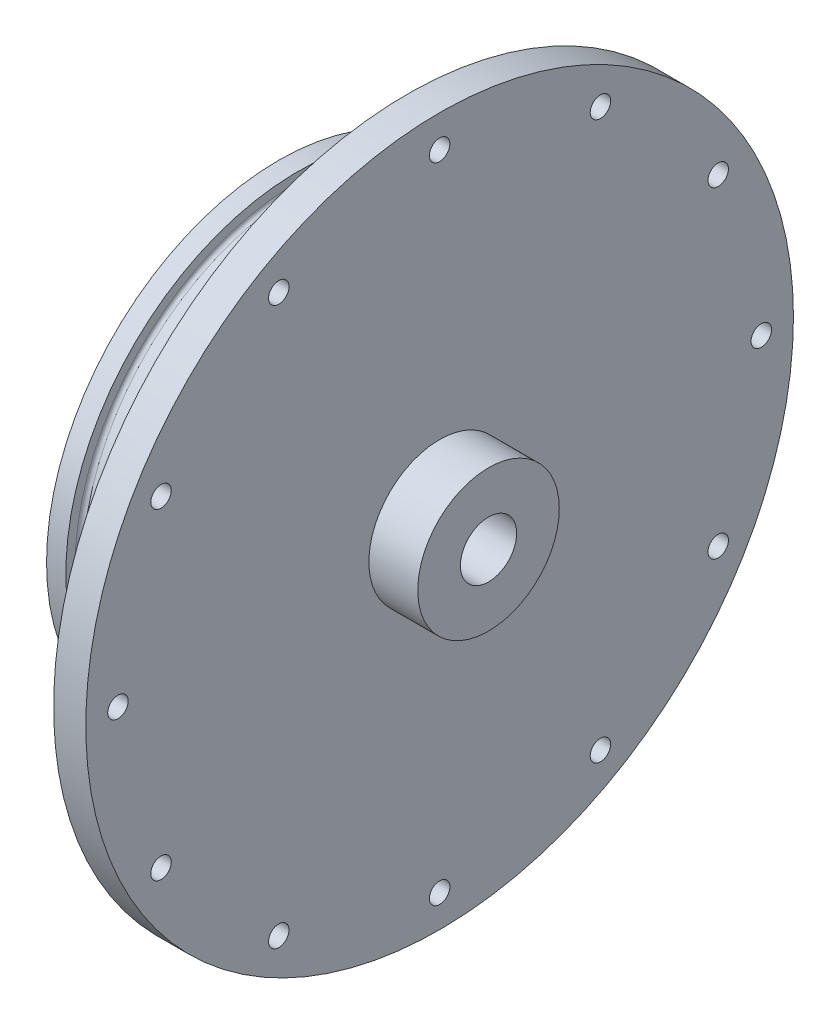
SolidWorks part; units mm, degrees
material "7075-T6 (SN)"
ref_plane "Front Plane" through (0, 0, 0) normal (0, 0, 1) x (1, 0, 0)
ref_plane "Top Plane" through (0, 0, 0) normal (0, 1, 0) x (1, 0, 0)
ref_plane "Right Plane" through (0, 0, 0) normal (1, 0, 0) x (0, 0, -1)
sketch "Sketch1" plane through (0, 0, 0) normal (1, 0, 0) x (0, 0, -1)
  circle A0 centre (0, 0) radius 69.85
  dimension "D1" = 139.7
extrude "Boss-Extrude1" add sketch "Sketch1" along normal blind 6.35
sketch "Sketch2" plane through (0, 0, 0) normal (-1, 0, 0) x (0, 0, 1)
  circle A0 centre (0, 0) radius 45.847
  dimension "D1" = 91.694
extrude "Boss-Extrude2" add sketch "Sketch2" along normal blind 25.4
sketch "Sketch10" plane through (0, 0, 0) normal (0, 1, 0) x (1, 0, 0)
  line L0 (0, 0) -> (-53.2238, 0) construction
  line L1 (-26.2636, 0) -> (26.2636, 0) construction
  line L2 (0, 0) -> (0, 64.5447) construction
  line L3 (0, -62.865) -> (0, 62.865) construction
ref_plane "Plane1" through (0, 0, -45.847) normal (0, 0, -1) x (-1, 0, 0)
sketch "Sketch11" plane through (0, 0, -45.847) normal (0, 0, -1) x (-1, 0, 0)
  line L0 (0, 0) -> (53.2238, 0) construction
  line L1 (0, -45.847) -> (0, 45.847) construction
  circle A0 centre (7.62, 0) radius 1.8986
  dimension "D2" = 3.7973
  dimension "D1" = 7.62
extrude "Cut-Extrude3" cut sketch "Sketch11" against normal blind 10.16
pattern_circular "CirPattern1" count 12 over 360 about axis through (0, 0, 0) along (-1, 0, 0) of "Cut-Extrude3" reverse direction yes
sketch "Sketch15" plane through (6.35, 0, 0) normal (1, 0, 0) x (0, 0, -1)
  circle A0 centre (0, 0) radius 5.5562
  dimension "D1" = 11.1125
extrude "Cut-Extrude4" cut sketch "Sketch15" against normal through all both and the other way through all
sketch "Sketch16" plane through (0, 0, 0) normal (0, 0, 1) x (1, 0, 0)
  line L0 (-9.5186, 45.847) -> (-25.4, 45.847) construction
  line L1 (-21.59, 45.847) -> (-14.4018, 45.847)
  line L2 (-21.59, 45.847) -> (-21.59, 44.069)
  line L3 (-20.828, 43.307) -> (-15.1638, 43.307)
  line L4 (-14.4018, 45.847) -> (-14.4018, 44.069)
  line L5 (0, 0) -> (-53.2238, 0) construction
  line L6 (-25.4, 45.847) -> (-25.4, -45.847) construction
  arc A0 (-14.4018, 44.069) -> (-15.1638, 43.307) centre (-15.1638, 44.069) cw
  arc A1 (-20.828, 43.307) -> (-21.59, 44.069) centre (-20.828, 44.069) cw
  point P8 (-26.6119, 0)
  point P13 (-14.4018, 43.307)
  point P16 (-21.59, 43.307)
  dimension "D4" = 0.762
  dimension "D1" = 43.307
  dimension "D2" = 3.81
  dimension "D3" = 7.1882
revolve "Cut-Revolve1" cut sketch "Sketch16" angle 360 about L0
sketch "Sketch17" plane through (6.35, 0, 0) normal (1, 0, 0) x (0, 0, -1)
  circle A0 centre (0, 0) radius 13.97
  circle A1 centre (0, 0) radius 5.5562
  dimension "D1" = 27.94
  dimension "D2" = 11.1125
extrude "Boss-Extrude3" add sketch "Sketch17" along normal blind 9.652
cosmetic thread "Cosmetic Thread1" parameters "D2"=23.1953
sketch "Sketch18" plane through (-25.4, 0, 0) normal (-1, 0, 0) x (0, 0, 1)
  circle A0 centre (0, 0) radius 38.2905
  dimension "D1" = 76.581
extrude "Cut-Extrude5" cut sketch "Sketch18" against normal blind 6.604
sketch "Sketch19" plane through (-18.796, 0, 0) normal (-1, 0, 0) x (0, 0, 1)
  line L0 (0, 0) -> (0, 69.85) construction
  circle A0 centre (0, 0) radius 69.85 construction
  circle A1 centre (0, 33.3375) radius 1.1303
  circle A2 centre (23.5732, 23.5732) radius 1.1303
  circle A3 centre (33.3375, 0) radius 1.1303
  circle A4 centre (23.5732, -23.5732) radius 1.1303
  circle A5 centre (0, -33.3375) radius 1.1303
  circle A6 centre (-23.5732, -23.5732) radius 1.1303
  circle A7 centre (-33.3375, 0) radius 1.1303
  circle A8 centre (-23.5732, 23.5732) radius 1.1303
  point P24 (0, 0)
  dimension "D2" = 2.2606
  dimension "D1" = 33.3375
  dimension "D3" = 8
extrude "Cut-Extrude6" cut sketch "Sketch19" against normal blind 6.35
sketch "Sketch20" plane through (-18.796, 0, 0) normal (-1, 0, 0) x (0, 0, 1)
  circle A0 centre (0, 0) radius 23.495
  dimension "D1" = 46.99
extrude "Cut-Extrude7" cut sketch "Sketch20" against normal blind 19.05
fillet "Fillet1" radius 2.54 1 edges at (0.254, 0, 23.495)
chamfer "Chamfer1" distance 5.08 angle 45 1 edges at (0.254, 0, 5.5562)
sketch "Sketch21" plane through (6.35, 0, 0) normal (1, 0, 0) x (0, 0, -1)
  line L0 (0, 0) -> (0, 75.052) construction
  circle A0 centre (0, 63.5) radius 2.0193
  circle A1 centre (31.75, 54.9926) radius 2.0193
  circle A2 centre (54.9926, 31.75) radius 2.0193
  circle A3 centre (63.5, 0) radius 2.0193
  circle A4 centre (54.9926, -31.75) radius 2.0193
  circle A5 centre (31.75, -54.9926) radius 2.0193
  circle A6 centre (0, -63.5) radius 2.0193
  circle A7 centre (-31.75, -54.9926) radius 2.0193
  circle A8 centre (-54.9926, -31.75) radius 2.0193
  circle A9 centre (-63.5, 0) radius 2.0193
  circle A10 centre (-54.9926, 31.75) radius 2.0193
  circle A11 centre (-31.75, 54.9926) radius 2.0193
  point P29 (0, 0)
  dimension "D2" = 4.0386
  dimension "D1" = 63.5
  dimension "D3" = 12
extrude "Cut-Extrude8" cut sketch "Sketch21" against normal through all
